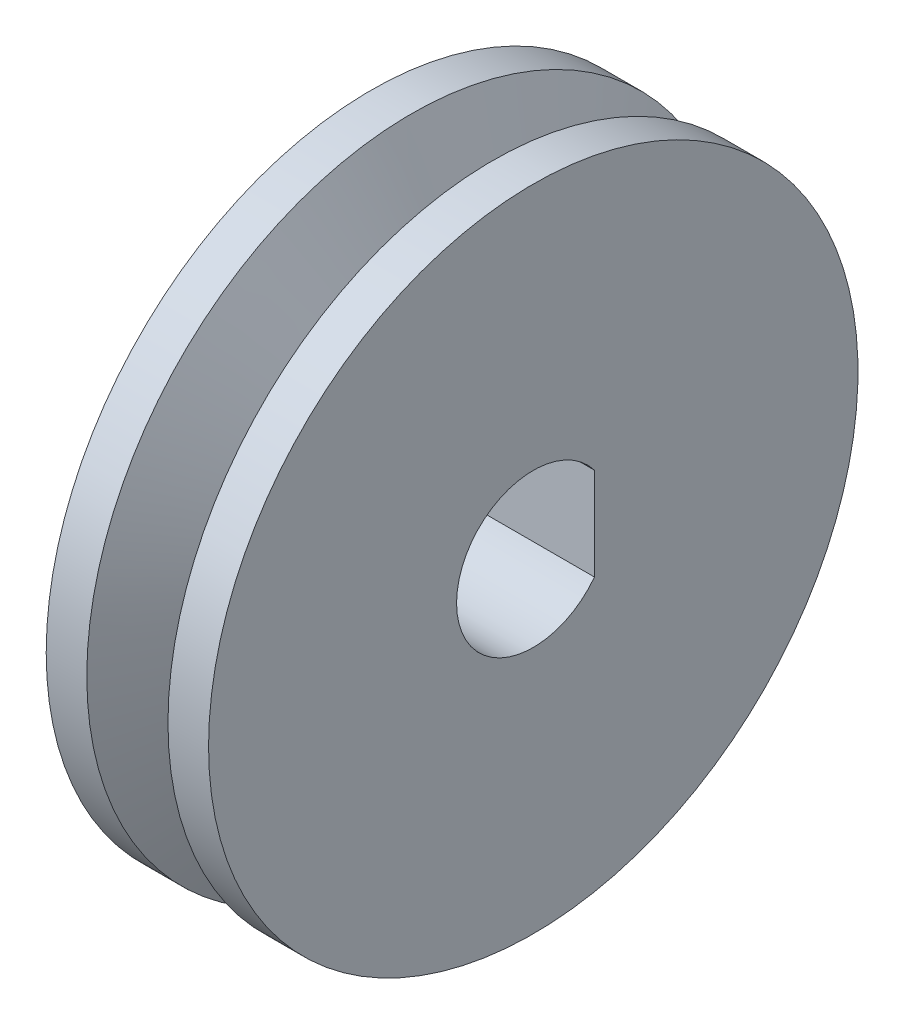
SolidWorks part; units mm, degrees
ref_plane "Front Plane" through (0, 0, 0) normal (0, 0, 1) x (1, 0, 0)
ref_plane "Top Plane" through (0, 0, 0) normal (0, 1, 0) x (1, 0, 0)
ref_plane "Right Plane" through (0, 0, 0) normal (1, 0, 0) x (0, 0, -1)
sketch "Sketch2" plane through (0, 0, 0) normal (0, 0, 1) x (1, 0, 0)
  line L0 (0, 0) -> (28.9983, 0) construction
  line L1 (0, 0) -> (0, 12.7)
  line L2 (0, 12.7) -> (1.5875, 12.7)
  line L3 (1.5875, 12.7) -> (3.175, 9.525)
  line L4 (3.175, 9.525) -> (4.7625, 12.7)
  line L5 (4.7625, 12.7) -> (6.35, 12.7)
  line L6 (6.35, 12.7) -> (6.35, 0)
  line L7 (0, 9.525) -> (6.35, 9.525) construction
  line L8 (0, 0) -> (6.35, 0)
  dimension "D1" = 1.5875
  dimension "D2" = 12.7
  dimension "D3" = 6.35
  dimension "D4" = 3.175
revolve "Revolve1" add sketch "Sketch2" angle 360 about L0
sketch "Sketch3" plane through (6.35, 0, 0) normal (1, 0, 0) x (0, 0, -1)
  line L0 (2.3929, -1.8094) -> (2.3929, 1.8094)
  line L1 (3, 2.5745) -> (3, -1.9178) construction
  arc A0 (2.3929, 1.8094) -> (2.3929, -1.8094) centre (0, 0) ccw
  arc A1 (2.3929, 1.8094) -> (2.3929, -1.8094) centre (0, 0) cw construction
  dimension "D2" = 3
  dimension "D1" = 0.6071
extrude "Cut-Extrude1" cut sketch "Sketch3" against normal through all both and the other way through all
